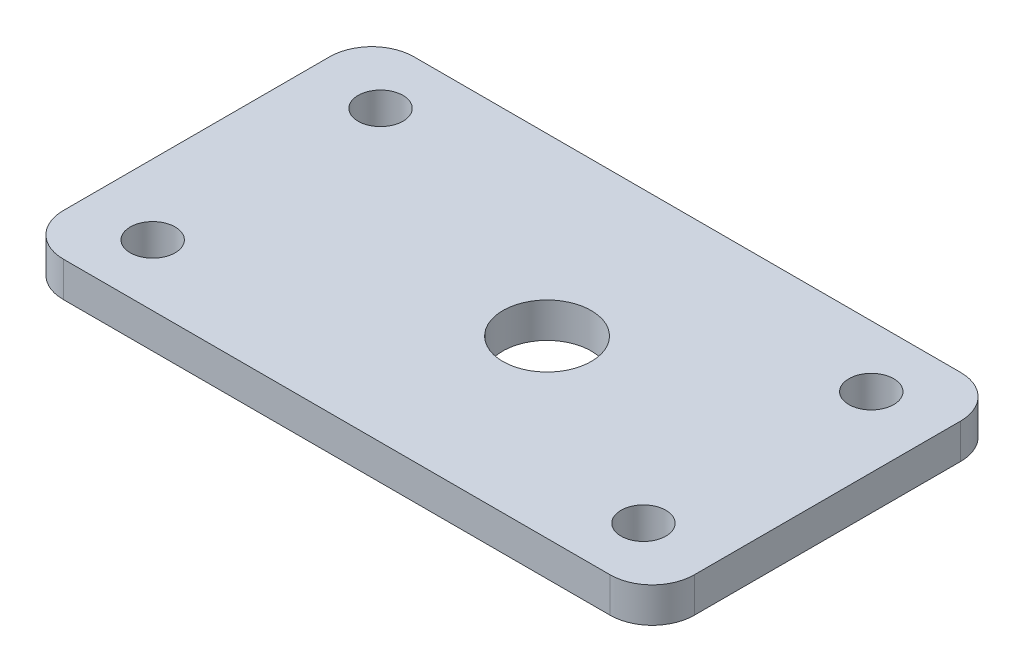
SolidWorks part; units mm, degrees
ref_plane "Front Plane" through (0, 0, 0) normal (0, 0, 1) x (1, 0, 0)
ref_plane "Top Plane" through (0, 0, 0) normal (0, 1, 0) x (1, 0, 0)
ref_plane "Right Plane" through (0, 0, 0) normal (1, 0, 0) x (0, 0, -1)
sketch "Sketch1" plane through (0, 0, 0) normal (0, 1, 0) x (1, 0, 0)
  line L0 (0, 0) -> (3.175, 0) construction
  line L1 (28.575, -15.875) -> (-28.575, -15.875)
  line L2 (28.575, -15.875) -> (28.575, 15.875)
  line L3 (28.575, 15.875) -> (-28.575, 15.875)
  line L4 (-28.575, -15.875) -> (-28.575, 15.875)
  line L5 (28.575, -15.875) -> (-28.575, 15.875) construction
  line L6 (28.575, 15.875) -> (-28.575, -15.875) construction
  circle A2 centre (3.175, 0) radius 4
  point P0 (0, 0)
  dimension "D3" = 8
  dimension "D4" = 31.75
  dimension "D1" = 57.15
  dimension "D2" = 31.75
extrude "Boss-Extrude1" add sketch "Sketch1" along normal blind 3.175 contours L3 L4 L1 L2 | A2
fillet "Fillet1" radius 3.81 4 edges at (28.575, 1.5875, -15.875) (28.575, 1.5875, 15.875) (-28.575, 1.5875, 15.875) (-28.575, 1.5875, -15.875)
sketch "Sketch2" plane through (0, 0, 0) normal (0, -1, 0) x (1, 0, 0)
  circle A0 centre (22.225, -10.3187) radius 2.032 construction
  circle A1 centre (22.225, 10.3188) radius 2.032 construction
  circle A2 centre (-22.225, -10.3188) radius 2.032 construction
  circle A3 centre (-22.225, 10.3187) radius 2.032 construction
  circle A4 centre (22.225, -10.3187) radius 2.032
  circle A5 centre (22.225, 10.3188) radius 2.032
  circle A6 centre (-22.225, -10.3188) radius 2.032
  circle A7 centre (-22.225, 10.3187) radius 2.032
extrude "Cut-Extrude1" cut sketch "Sketch2" against normal through all
